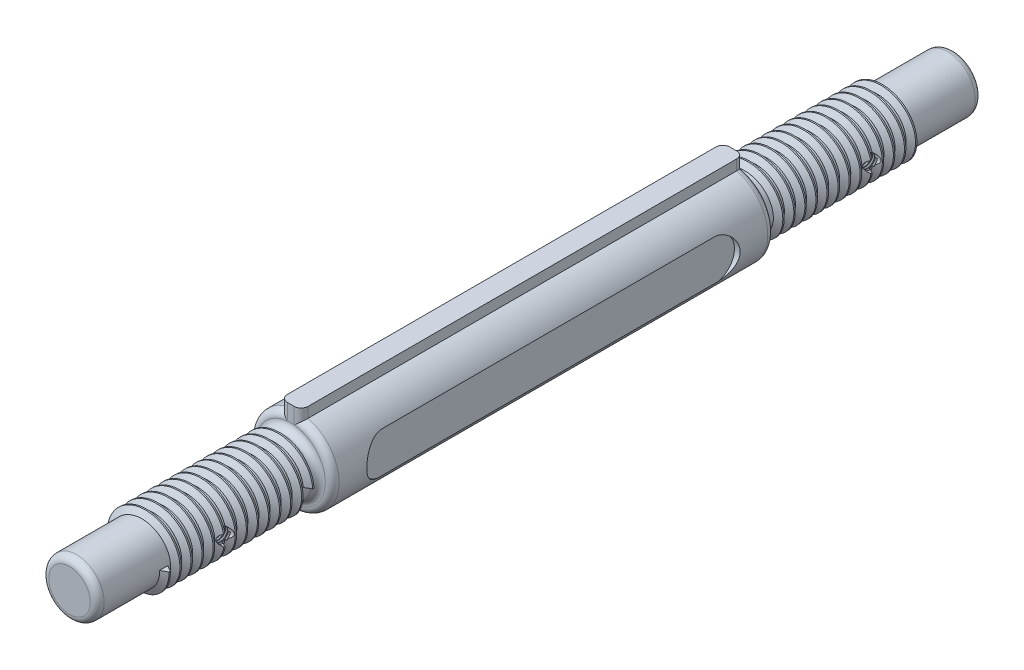
SolidWorks part; units mm, degrees
material "AISI 1020"
ref_plane "Front Plane" through (0, 0, 0) normal (0, 0, 1) x (1, 0, 0)
ref_plane "Top Plane" through (0, 0, 0) normal (0, 1, 0) x (1, 0, 0)
ref_plane "Right Plane" through (0, 0, 0) normal (1, 0, 0) x (0, 0, -1)
sketch "Sketch1" plane through (0, 0, 0) normal (0, 0, 1) x (1, 0, 0)
  line L0 (-1.1906, 4.6113) -> (-1.1906, 5.8019)
  line L1 (-1.1906, 5.8019) -> (1.1906, 5.8019)
  line L2 (1.1906, 5.8019) -> (1.1906, 4.6113)
  arc A1 (-1.1906, 4.6113) -> (1.1906, 4.6113) centre (0, 0) ccw
  point P2 (0, 5.8019)
  dimension "D1" = 4.7625
  dimension "D2" = 1.1906
  dimension "D3" = 2.3813
extrude "Boss-Extrude1" add sketch "Sketch1" along normal blind 50.8
sketch "Sketch2" plane through (0, 0, 50.8) normal (0, 0, 1) x (1, 0, 0)
  circle A0 centre (0, 0) radius 3.175
  dimension "D1" = 6.35
extrude "Boss-Extrude2" add sketch "Sketch2" along normal blind 25.4
fillet "Fillet2" radius 0.7937 4 edges at (1.1906, 5.2066, 0) (-1.1906, 5.2066, 0) (1.1906, 5.2066, 50.8) (-1.1906, 5.2066, 50.8)
fillet "Fillet4" radius 0.7937 2 edges at (0, -4.7625, 50.8) (3.175, 0, 50.8)
sketch "Sketch3" plane through (0, 0, 0) normal (0, 0, -1) x (-1, 0, 0)
  circle A0 centre (0, 0) radius 3.175
  dimension "D1" = 6.35
extrude "Boss-Extrude3" add sketch "Sketch3" along normal blind 25.4
fillet "Fillet5" radius 0.7937 2 edges at (0, -4.7625, 0) (3.175, 0, 0)
ref_plane "Plane1" through (5.9531, 0, 0) normal (1, 0, 0) x (0, 0, -1)
sketch "Sketch4" plane through (5.9531, 0, 0) normal (1, 0, 0) x (0, 0, -1)
  line L0 (-50.0062, -0.0756) -> (-0.7938, -0.0756) construction
  line L1 (-50.0062, 4.6113) -> (-50.0062, -4.7625) construction
  line L2 (-0.7938, -4.7625) -> (-0.7938, 4.6113) construction
  line L3 (-44.45, -0.0756) -> (-6.35, -0.0756) construction
  line L4 (-44.45, 2.3056) -> (-6.35, 2.3056)
  line L5 (-44.45, -2.4569) -> (-6.35, -2.4569)
  arc A0 (-44.45, 2.3056) -> (-44.45, -2.4569) centre (-44.45, -0.0756) ccw
  arc A1 (-6.35, -2.4569) -> (-6.35, 2.3056) centre (-6.35, -0.0756) ccw
  point P8 (-25.4, -0.0756)
  point P13 (-25.4, -0.0756)
  dimension "D1" = 2.3813
  dimension "D2" = 19.05
extrude "Cut-Extrude1" cut sketch "Sketch4" against normal blind 1.8415
thread "Thread2" pitch 1.27 method extrude profile "Thread Profile2" start angle 0, offset 0, length 0, pitch 1.27, diameter 6.35
ref_plane "Plane3" through (-3.175, 0, -0.7937) normal (0, -1, 0) x (-1, 0, 0)
sketch "Thread Profile2" plane through (-3.175, 0, -0.7937) normal (0, -1, 0) x (-1, 0, 0)
  line L0 (0, 0) -> (0, 1.27) construction
  line L1 (0, 0) -> (0.6874, 0.3969)
  line L2 (0.6874, 0.3969) -> (0.6874, 0.5556)
  line L3 (0.6874, 0.5556) -> (0, 0.9525)
  line L4 (0.6874, 0.4762) -> (0, 0.4762) construction
  line L11 (0, 0) -> (0, 0.9525)
  point P2 (0, 0)
  dimension "Pitch" = 1.27
  dimension "Profile_Angle" = 60
  dimension "Profile_Land" = 0.1588
  dimension "Profile_Height" = 0.6874
thread "Thread3" pitch 1.27 method extrude profile "Thread Profile3" start angle 0, offset 0, length 0, pitch 1.27, diameter 6.35
ref_plane "Plane4" through (3.175, 0, 51.5938) normal (0, -1, 0) x (1, 0, 0)
sketch "Thread Profile3" plane through (3.175, 0, 51.5938) normal (0, -1, 0) x (1, 0, 0)
  line L0 (0, 0) -> (0, 1.27) construction
  line L1 (0, 0) -> (0.6874, 0.3969)
  line L2 (0.6874, 0.3969) -> (0.6874, 0.5556)
  line L3 (0.6874, 0.5556) -> (0, 0.9525)
  line L4 (0.6874, 0.4762) -> (0, 0.4762) construction
  line L11 (0, 0) -> (0, 0.9525)
  point P2 (0, 0)
  dimension "Pitch" = 1.27
  dimension "Profile_Angle" = 60
  dimension "Profile_Land" = 0.1588
  dimension "Profile_Height" = 0.6874
sketch "Sketch6" plane through (5.9531, 0, 0) normal (1, 0, 0) x (0, 0, -1)
  line L0 (-0.7938, 4.6113) -> (-0.7938, -4.7625) construction
  line L1 (-50.0062, 4.6113) -> (-50.0062, -4.7625) construction
  circle A0 centre (12.4142, -0.0756) radius 0.7937
  circle A1 centre (-61.8649, -0.0756) radius 0.7937
  point P6 (-0.7938, -0.0756)
  dimension "D1" = 1.5875
  dimension "D3" = 1.5875
  dimension "D2" = 13.208
  dimension "D4" = 11.8586
extrude "Cut-Extrude2" cut sketch "Sketch6" against normal blind 4.445
thread "Thread1" pitch 0.3175 method cut profile "Thread Profile1" start angle 0, offset 0, length 0, pitch 0.3175, diameter 1.5875
ref_plane "Plane2" through (1.5081, -0.0756, -13.208) normal (0, -1, 0) x (0, 0, -1)
sketch "Thread Profile1" plane through (1.5081, -0.0756, -13.208) normal (0, -1, 0) x (0, 0, -1)
  line L0 (0, 0) -> (0, 0.3175) construction
  line L1 (0, 0) -> (0.1719, 0.0992)
  line L2 (0.1719, 0.0992) -> (0.1719, 0.1389)
  line L3 (0.1719, 0.1389) -> (0, 0.2381)
  line L4 (0.1719, 0.1191) -> (0, 0.1191) construction
  line L11 (0, 0) -> (0, 0.2381)
  point P2 (0, 0)
  dimension "Pitch" = 0.3175
  dimension "Profile_Angle" = 60
  dimension "Profile_Land" = 0.0397
  dimension "Profile_Height" = 0.1719
fillet "Fillet6" radius 0.7937 2 edges at (3.175, 0, 76.2) (-3.175, 0, -25.4)
thread "Thread4" pitch 0.3175 method cut profile "Thread Profile4" start angle 0, offset 0, length 0, pitch 0.3175, diameter 1.5875
ref_plane "Plane5" through (1.5081, -0.0756, 61.0711) normal (0, -1, 0) x (0, 0, -1)
sketch "Thread Profile4" plane through (1.5081, -0.0756, 61.0711) normal (0, -1, 0) x (0, 0, -1)
  line L0 (0, 0) -> (0, 0.3175) construction
  line L1 (0, 0) -> (0.1719, 0.0992)
  line L2 (0.1719, 0.0992) -> (0.1719, 0.1389)
  line L3 (0.1719, 0.1389) -> (0, 0.2381)
  line L4 (0.1719, 0.1191) -> (0, 0.1191) construction
  line L11 (0, 0) -> (0, 0.2381)
  point P2 (0, 0)
  dimension "Pitch" = 0.3175
  dimension "Profile_Angle" = 60
  dimension "Profile_Land" = 0.0397
  dimension "Profile_Height" = 0.1719
